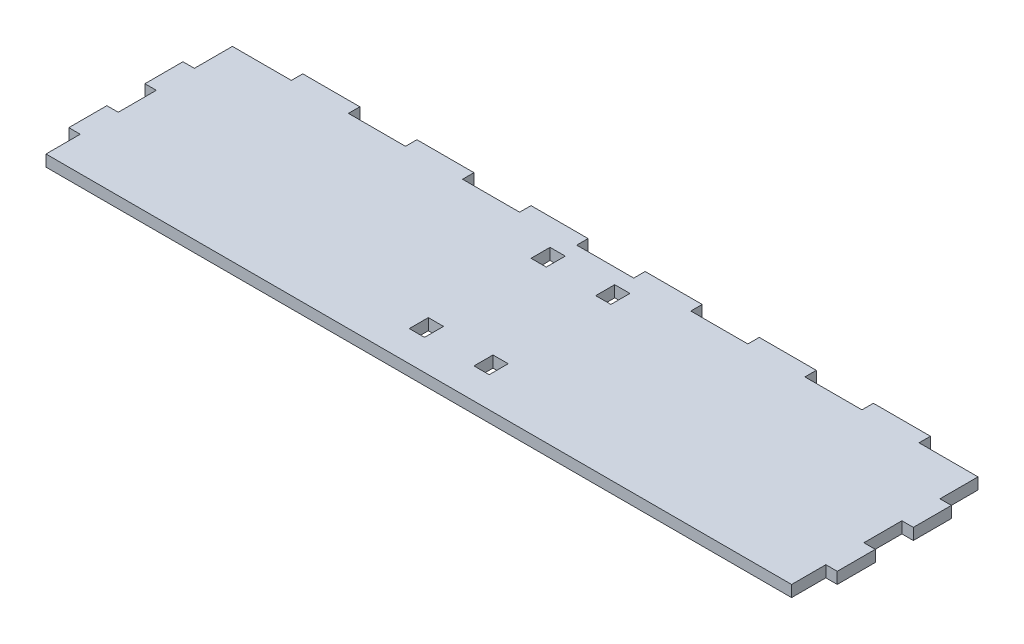
SolidWorks part; units mm, degrees
ref_plane "Front Plane" through (0, 0, 0) normal (0, 0, 1) x (1, 0, 0)
ref_plane "Top Plane" through (0, 0, 0) normal (0, 1, 0) x (1, 0, 0)
ref_plane "Right Plane" through (0, 0, 0) normal (1, 0, 0) x (0, 0, -1)
sketch "Sketch1" plane through (0, 0, 0) normal (0, 1, 0) x (1, 0, 0)
  line L0 (15, 0) -> (-0.5, 0)
  line L1 (15, 0) -> (15, 3)
  line L2 (15, 3) -> (30, 3)
  line L3 (30, 3) -> (30, 0)
  line L4 (30, 0) -> (45, 0)
  line L5 (45, 0) -> (45, 3)
  line L6 (45, 3) -> (60, 3)
  line L7 (60, 3) -> (60, 0)
  line L8 (60, 0) -> (75, 0)
  line L9 (75, 0) -> (75, 3)
  line L10 (75, 3) -> (90, 3)
  line L11 (90, 3) -> (90, 0)
  line L12 (90, 0) -> (105, 0)
  line L13 (105, 0) -> (105, 3)
  line L14 (105, 3) -> (120, 3)
  line L15 (120, 3) -> (120, 0)
  line L16 (120, 0) -> (135, 0)
  line L17 (135, 0) -> (135, 3)
  line L18 (135, 3) -> (150, 3)
  line L19 (150, 3) -> (150, 0)
  line L20 (150, 0) -> (165, 0)
  line L21 (165, 0) -> (165, 3)
  line L22 (165, 3) -> (180, 3)
  line L23 (180, 3) -> (180, 0)
  line L24 (180, 0) -> (195.5, 0)
  line L25 (-0.5, 0) -> (-0.5, -10)
  line L26 (-0.5, -10) -> (-3.5, -10)
  line L27 (-3.5, -10) -> (-3.5, -20)
  line L28 (-3.5, -20) -> (-0.5, -20)
  line L29 (-0.5, -20) -> (-0.5, -30)
  line L30 (-0.5, -30) -> (-3.5, -30)
  line L31 (-3.5, -30) -> (-3.5, -40)
  line L32 (-3.5, -40) -> (-0.5, -40)
  line L33 (-0.5, -40) -> (-0.5, -49)
  line L34 (-0.5, -49) -> (195.5, -49)
  line L35 (97.5, 0) -> (97.5, -49) construction
  line L36 (195.5, -40) -> (195.5, -49)
  line L37 (198.5, -40) -> (195.5, -40)
  line L38 (198.5, -30) -> (198.5, -40)
  line L39 (195.5, -30) -> (198.5, -30)
  line L40 (195.5, -20) -> (195.5, -30)
  line L41 (198.5, -20) -> (195.5, -20)
  line L42 (198.5, -10) -> (198.5, -20)
  line L43 (195.5, -10) -> (198.5, -10)
  line L44 (195.5, 0) -> (195.5, -10)
  dimension "D1" = 6
  dimension "D2" = 15
  dimension "D3" = 3
  dimension "D4" = 3
  dimension "D6" = 15.5
  dimension "D7" = 10
  dimension "D8" = 10
  dimension "D9" = 3
  dimension "D10" = 10
  dimension "D11" = 10
  dimension "D12" = 9
extrude "Boss-Extrude1" add sketch "Sketch1" along normal blind 3
sketch "Sketch2" plane through (0, 3, 0) normal (0, 1, 0) x (1, 0, 0)
  line L0 (97.5, 0) -> (97.5, -49) construction
  line L1 (105, 0) -> (90, 0) construction
  line L2 (-0.5, -49) -> (195.5, -49) construction
  line L3 (97.5, -24.5) -> (91, -24.5) construction
  line L4 (108, -36) -> (108, -41)
  line L5 (91, -36) -> (87, -36)
  line L6 (91, -36) -> (91, -41)
  line L7 (91, -41) -> (87, -41)
  line L8 (87, -36) -> (87, -41)
  line L9 (104, -41) -> (108, -41)
  line L10 (104, -36) -> (104, -41)
  line L11 (104, -36) -> (108, -36)
  line L12 (108, -9) -> (108, -4)
  line L13 (91, -9) -> (87, -9)
  line L14 (91, -9) -> (91, -4)
  line L15 (91, -4) -> (87, -4)
  line L16 (87, -9) -> (87, -4)
  line L17 (104, -4) -> (108, -4)
  line L18 (104, -9) -> (104, -4)
  line L19 (104, -9) -> (108, -9)
  dimension "D1" = 6.5
  dimension "D2" = 4
  dimension "D3" = 5
  dimension "D4" = 6.5
  dimension "D5" = 8
  dimension "D6" = 4
  dimension "D7" = 5
  dimension "D8" = 40
extrude "Cut-Extrude1" cut sketch "Sketch2" against normal blind 10
